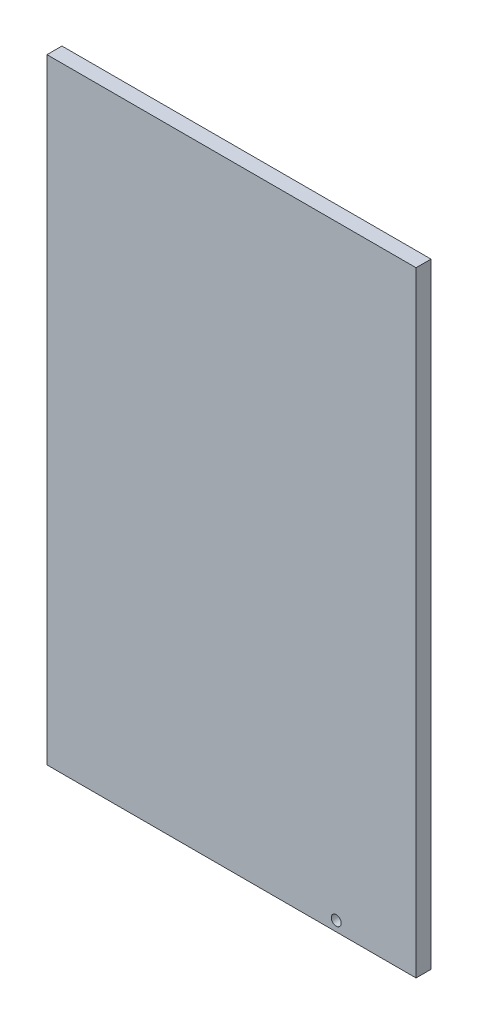
SolidWorks part; units mm, degrees
material "Perspex (TM) GS Acrylic Cast Sheet"
ref_plane "Front Plane" through (0, 0, 0) normal (0, 0, 1) x (1, 0, 0)
ref_plane "Top Plane" through (0, 0, 0) normal (0, 1, 0) x (1, 0, 0)
ref_plane "Right Plane" through (0, 0, 0) normal (1, 0, 0) x (0, 0, -1)
sketch "Sketch1" plane through (0, 0, 0) normal (0, 0, 1) x (1, 0, 0)
  line L1 (-111, -185) -> (111, -185)
  line L2 (-111, -185) -> (-111, 185)
  line L3 (-111, 185) -> (111, 185)
  line L4 (111, -185) -> (111, 185)
  line L5 (-111, -185) -> (111, 185) construction
  line L6 (-111, 185) -> (111, -185) construction
  point P0 (0, 0)
  dimension "D1" = 222
  dimension "D2" = 370
extrude "Boss-Extrude1" add sketch "Sketch1" along normal blind 9
sketch "Sketch2" plane through (0, 0, 9) normal (0, 0, 1) x (1, 0, 0)
  line L0 (111, -185) -> (111, 185) construction
  line L1 (-111, -185) -> (111, -185) construction
  circle A0 centre (63, -179) radius 3
  dimension "D1" = 6
  dimension "D2" = 48
  dimension "D3" = 6
extrude "Cut-Extrude1" cut sketch "Sketch2" against normal through all
sketch "Sketch4" [suppressed] plane through (0, 0, 0) normal (0, 0, -1) x (-1, 0, 0)
  circle A0 centre (-30, -170) radius 5.5
  circle A1 centre (-90, -170) radius 5.5
  circle A2 centre (30, -170) radius 5.5
  circle A3 centre (90, -170) radius 5.5
  dimension "D1" = 11
extrude "Cut-Extrude2" [suppressed] cut sketch "Sketch4" against normal through all
equation "\"PCLength\"= 145mm'Length across I/O from PS to GPU"
equation "\"PCWidth\"= 340mm'Distance of longest part parallel to GPU(ussually GPU)"
equation "\"PCHeight\"= 180mm'Tallest point with mobo laying flat"
equation "\"WallThickness\"= 9mm'Thickness of each outer tank wall"
equation "\"ThermoBarrierThickness\"= 6mm'Thickness of barrier between hot side and cold side"
equation "\"HotSideGap\"= 36mm'Space in the hot side for a pump"
equation "\"PCClearance\"= 30mm'Clearance from top of tank to top of PC"
equation "\"RadiatorHeight\"= 275mm'Final Height from ground of radiators"
equation "\"D1@Sketch1\"=\"PCHeight\" + \"ThermoBarrierThickness\" + \"HotSideGap\""
equation "\"D2@Sketch1\"=\"PCWidth\" + \"PCClearance\""
equation "\"D1@Boss-Extrude1\"=\"WallThickness\""
equation "\"D2@Sketch2\"=\"HotSideGap\" + \"ThermoBarrierThickness\" + 6"
